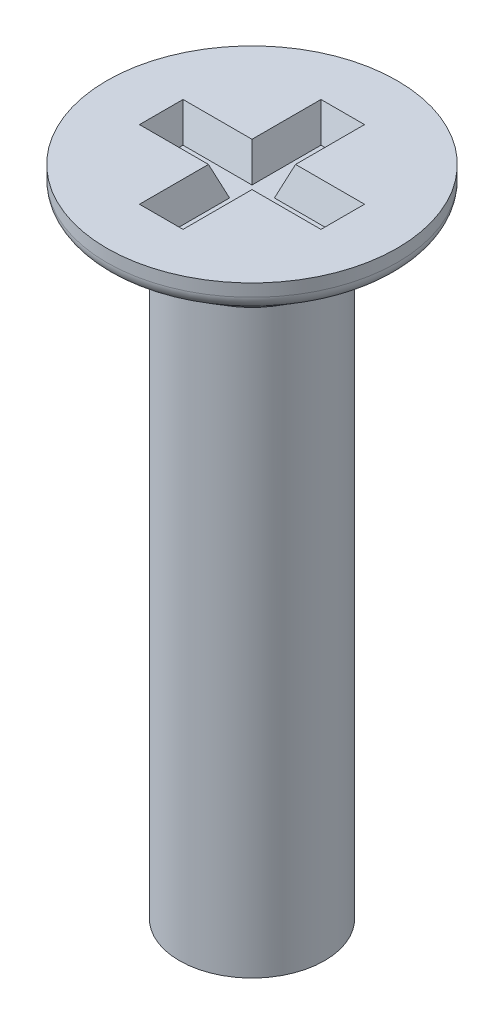
SolidWorks part; units mm, degrees
ref_plane "Front Plane" through (0, 0, 0) normal (0, 0, 1) x (1, 0, 0)
ref_plane "Top Plane" through (0, 0, 0) normal (0, 1, 0) x (1, 0, 0)
ref_plane "Right Plane" through (0, 0, 0) normal (1, 0, 0) x (0, 0, -1)
sketch "Sketch1" plane through (0, 0, 0) normal (0, 1, 0) x (1, 0, 0)
  circle A0 centre (0, 0) radius 1
  dimension "D1" = 2
extrude "Boss-Extrude1" add sketch "Sketch1" along normal blind 0.5
sketch "Sketch2" plane through (0, 0.5, 0) normal (0, 1, 0) x (1, 0, 0)
  line L0 (-0.15, 0.625) -> (-0.15, 0.15)
  line L1 (-0.625, 0.625) -> (0.625, 0.625) construction
  line L2 (-0.625, 0.625) -> (-0.625, -0.625) construction
  line L3 (-0.625, -0.625) -> (0.625, -0.625) construction
  line L4 (0.625, 0.625) -> (0.625, -0.625) construction
  line L5 (-0.15, 0.15) -> (-0.625, 0.15)
  line L6 (-0.625, 0.15) -> (-0.625, -0.15)
  line L7 (-0.625, -0.15) -> (-0.15, -0.15)
  line L8 (-0.15, -0.15) -> (-0.15, -0.625)
  line L9 (-0.15, -0.625) -> (0.15, -0.625)
  line L10 (0.15, -0.625) -> (0.15, -0.15)
  line L11 (0.15, -0.15) -> (0.625, -0.15)
  line L12 (0.625, -0.15) -> (0.625, 0.15)
  line L13 (0.625, 0.15) -> (0.15, 0.15)
  line L14 (0.15, 0.15) -> (0.15, 0.625)
  line L15 (0.15, 0.625) -> (-0.15, 0.625)
  line L16 (-0.15, 0.15) -> (0.15, -0.15) construction
  line L17 (-0.15, -0.15) -> (0.15, 0.15) construction
  point P4 (-0.625, 0)
  point P6 (0, 0.625)
  point P19 (0, 0)
  dimension "D1" = 1.25
  dimension "D2" = 0.3
extrude "Cut-Extrude1" cut sketch "Sketch2" against normal blind 0.2 draft 20
sketch "Sketch3" plane through (0, 0, 0) normal (0, -1, 0) x (1, 0, 0)
  circle A0 centre (0, 0) radius 0.5
  dimension "D1" = 1
extrude "Boss-Extrude2" add sketch "Sketch3" along normal blind 4
chamfer "Chamfer1" distance 0.5 angle 36 1 edges at (0, 0, 1) first distance on face at (0, 0, 1)
fillet "Fillet1" radius 0.1 1 edges at (0, 0.3633, 1)
